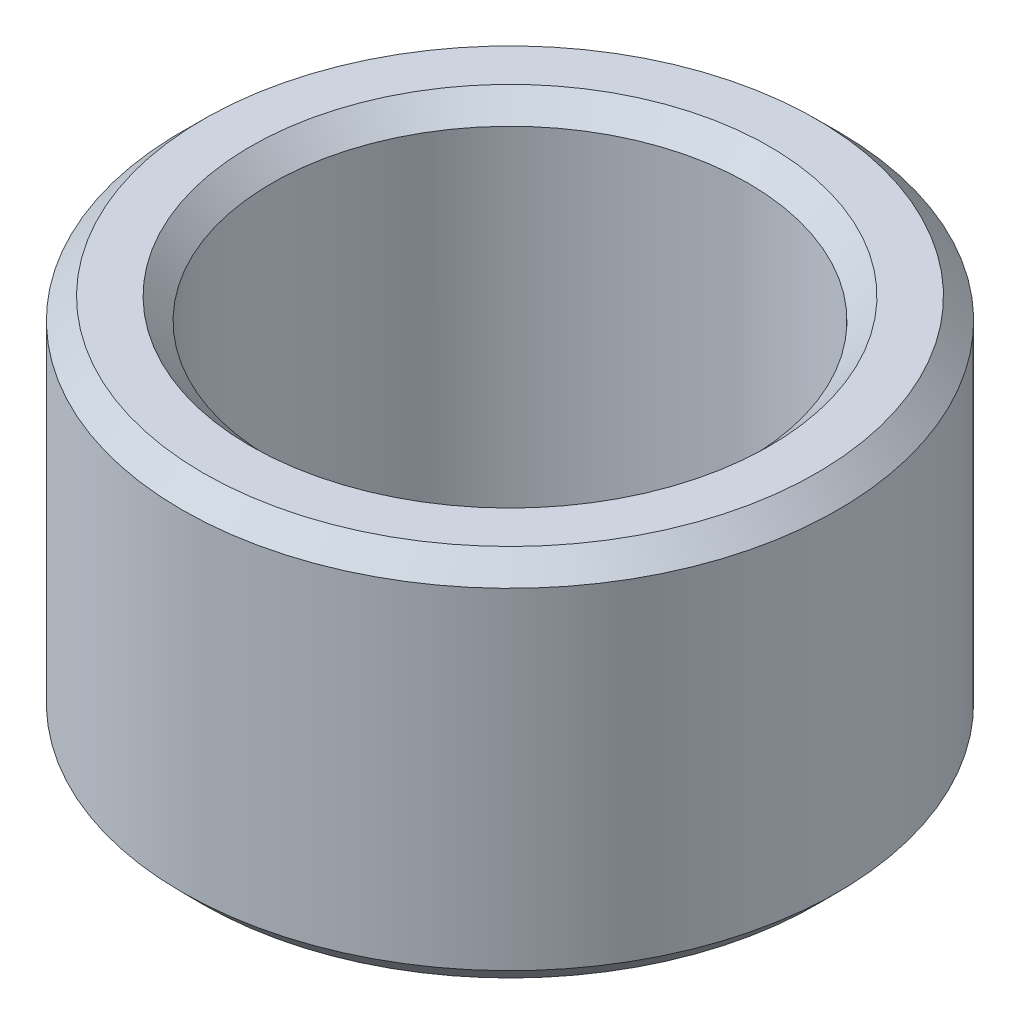
SolidWorks part; units mm, degrees
ref_plane "Front Plane" through (0, 0, 0) normal (0, 0, 1) x (1, 0, 0)
ref_plane "Top Plane" through (0, 0, 0) normal (0, 1, 0) x (1, 0, 0)
ref_plane "Right Plane" through (0, 0, 0) normal (1, 0, 0) x (0, 0, -1)
sketch "Sketch1" plane through (0, 0, 0) normal (0, 1, 0) x (1, 0, 0)
  circle A0 centre (0, 0) radius 25
  dimension "SLEEVE_OD" = 50
extrude "Boss-Extrude1" add sketch "Sketch1" along normal blind 28.4885
sketch "Sketch2" plane through (0, 0, 0) normal (0, 1, 0) x (1, 0, 0)
  circle A0 centre (0, 0) radius 18.1706
  dimension "BORE_D" = 36.3413
extrude "Cut-Extrude1" cut sketch "Sketch2" along normal through all
chamfer "Chamfer1" distance 1.6155 angle 45.168 4 edges at (0, 28.4885, 18.1706) (0, 0, 18.1706) (0, 0, 25) (0, 28.4885, 25) first distance on face at (0, 28.4885, 18.1706) first distance on face at (0, 0, 18.1706) first distance on face at (0, 28.4885, 25)
